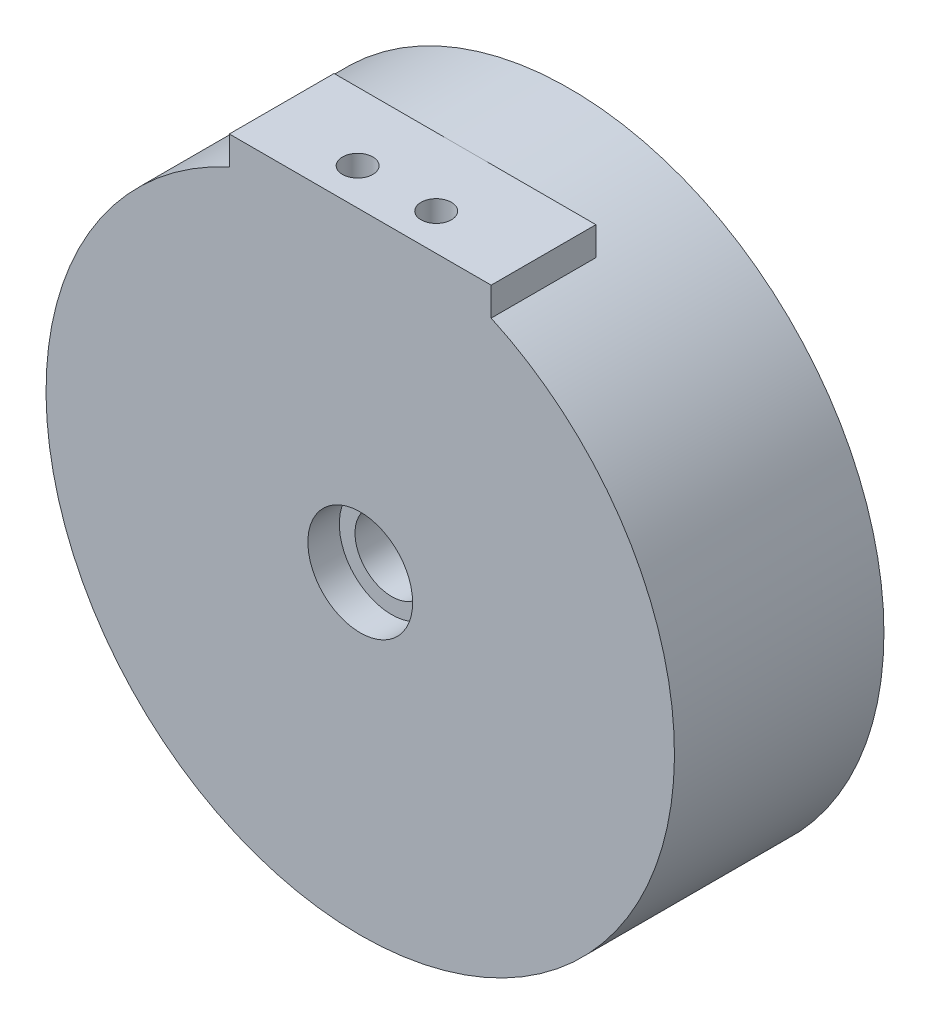
SolidWorks part; units mm, degrees
ref_plane "前视基准面" through (0, 0, 0) normal (0, 0, 1) x (1, 0, 0)
ref_plane "上视基准面" through (0, 0, 0) normal (0, 1, 0) x (1, 0, 0)
ref_plane "右视基准面" through (0, 0, 0) normal (1, 0, 0) x (0, 0, -1)
other "Configuration Table"
sketch "草图1" plane through (0, 0, 0) normal (0, 0, 1) x (1, 0, 0)
  circle A0 centre (0, 0) radius 30
  dimension "D1" = 60
extrude "凸台-拉伸1" add sketch "草图1" along normal blind 20
sketch "草图2" plane through (0, 0, 0) normal (0, 0, -1) x (-1, 0, 0)
  line L0 (0, 0) -> (0, 30) construction
  line L1 (-12.5, 30) -> (12.5, 30)
  line L2 (12.5, 30) -> (12.5, 27.2718)
  line L3 (-12.5, 30) -> (-12.5, 27.2718)
  circle A0 centre (0, 0) radius 30 construction
  arc A1 (-12.5, 27.2718) -> (0, 30) centre (0, 0) cw
  arc A2 (12.5, 27.2718) -> (0, 30) centre (0, 0) cw
  arc A3 (12.5, 27.2718) -> (0, 30) centre (0, 0) ccw
  circle M4 centre (0, 0) radius 30
  dimension "D1" = 12.5
extrude "凸台-拉伸2" add sketch "草图2" against normal blind 10 contours L2 L1 M4 | L1 L3 M4 region at (9.4041, 29.1883, 0) region at (-9.4041, 29.1883, 0)
sketch "草图3" plane through (0, 0, 10) normal (0, 0, 1) x (1, 0, 0)
  line L0 (-12.5, 27.2718) -> (-12.5, 30)
  line L1 (-12.5, 30) -> (12.5, 30)
  line L2 (12.5, 30) -> (12.5, 27.2718)
  arc A0 (-12.5, 27.2718) -> (0, 30) centre (0, 0) ccw
  arc A1 (0, 30) -> (12.3929, 27.3206) centre (0, 0) cw
  line M1 (-12.5, 30) -> (-12.5, 27.2718)
  arc M2 (-12.5, 27.2718) -> (0, 30) centre (0, 0) cw
  line M3 (0, 30) -> (-12.5, 30)
extrude "凸台-拉伸3" add sketch "草图3" along normal blind 10 contours M3 M1 M2 | A0 L2 L1 region at (-9.4041, 29.1883, 10) region at (9.4041, 29.1883, 10)
sketch "草图4" plane through (0, 0, 0) normal (0, 0, -1) x (-1, 0, 0)
  line L0 (-12.5, 27.2718) -> (-12.5, 30)
  line L1 (-12.5, 30) -> (12.5, 30)
  line L2 (12.5, 30) -> (12.5, 27.2718)
  arc A0 (-12.5, 27.2718) -> (0, 30) centre (0, 0) ccw
  arc A1 (12.5, 27.2718) -> (0, 30) centre (0, 0) ccw
  arc A2 (-12.5, 27.2718) -> (0, 30) centre (0, 0) cw
  line M2 (12.5, 27.2718) -> (12.5, 30)
  line M3 (12.5, 30) -> (-12.5, 30)
  line M4 (-12.5, 30) -> (-12.5, 27.2718)
extrude "切除-拉伸1" cut sketch "草图4" against normal blind 10 contours A2 L1 M4 | A0 M2 M3 region at (9.4041, 29.1883, 0) region at (-9.4041, 29.1883, 0)
sketch "草图5" plane through (0, 30, 0) normal (0, 1, 0) x (1, 0, 0)
  line L0 (-12.5, -13) -> (12.5, -13)
  line L2 (-3.75, -13) -> (-3.75, -20) construction
  line L3 (-12.5, -20) -> (-12.5, -10) construction
  line L5 (12.5, -20) -> (12.5, -10) construction
  line L7 (-7.5, -13) -> (-7.5, -20)
  line L9 (12.5, -20) -> (-12.5, -20) construction
  line L10 (0, -10) -> (0, -20)
  line L11 (7.5, -13) -> (7.5, -20)
  line L12 (3.75, -13) -> (3.75, -20) construction
  line L13 (-7.5, -16.5) -> (7.5, -16.5) construction
  circle A2 centre (-3.75, -16.5) radius 1.45
  circle A3 centre (3.75, -16.5) radius 1.45
  dimension "D1" = 3
  dimension "D4" = 2.9
  dimension "D2" = 5
  dimension "D3" = 3.75
extrude "切除-拉伸2" cut sketch "草图5" against normal blind 3 contours A2 | A3
sketch "草图7" plane through (0, 0, 20) normal (0, 0, 1) x (1, 0, 0)
  circle A0 centre (0, 0) radius 3.5
  dimension "D1" = 7
extrude "切除-拉伸4" cut sketch "草图7" against normal through all
sketch "草图8" plane through (0, 0, 20) normal (0, 0, 1) x (1, 0, 0)
  circle A0 centre (0, 0) radius 5
  dimension "D1" = 10
extrude "切除-拉伸5" cut sketch "草图8" against normal blind 3
